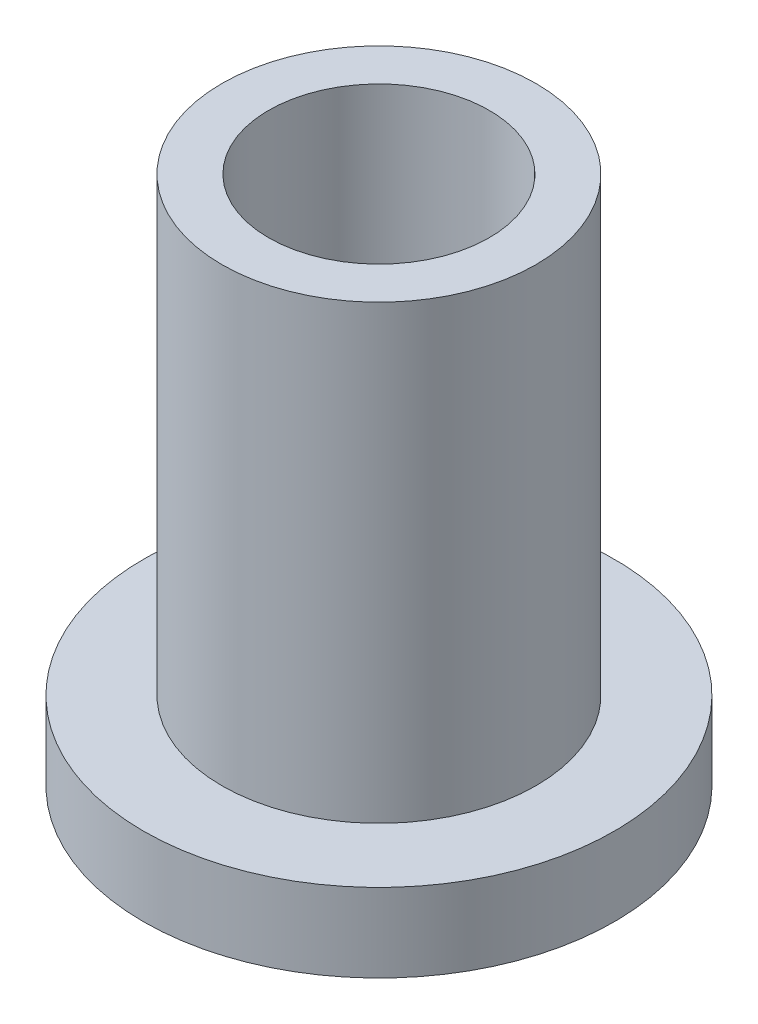
SolidWorks part; units mm, degrees
ref_plane "Front Plane" through (0, 0, 0) normal (0, 0, 1) x (1, 0, 0)
ref_plane "Top Plane" through (0, 0, 0) normal (0, 1, 0) x (1, 0, 0)
ref_plane "Right Plane" through (0, 0, 0) normal (1, 0, 0) x (0, 0, -1)
sketch "Sketch1" plane through (0, 0, 0) normal (0, 1, 0) x (1, 0, 0)
  circle A0 centre (0, 0) radius 7.62
  circle A1 centre (0, 0) radius 3.5719
  circle A2 centre (0, 0) radius 5.08
  dimension "D1" = 7.1437
  dimension "D2" = 10.16
  dimension "D3" = 15.24
extrude "Boss-Extrude1" add sketch "Sketch1" along normal blind 17.145 contours A2 A1 region at (-4.9363, 0, 0)
extrude "Boss-Extrude2" add sketch "Sketch1<3>" along normal blind 2.54 contours A0 A2 region at (-7.4045, 0, 0)
sketch "Sketch1<3>" plane through (0, 0, 0) normal (0, 1, 0) x (1, 0, 0) same geometry as "Sketch1"
